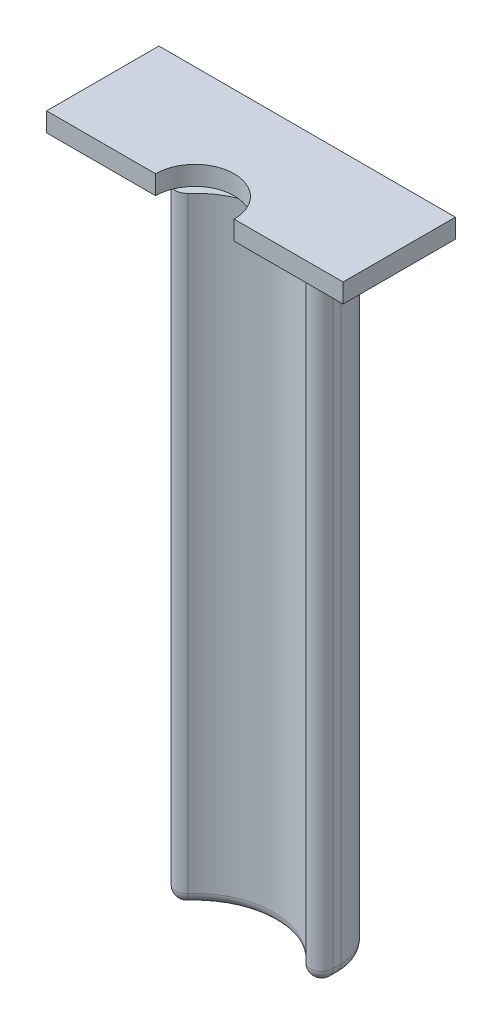
SolidWorks part; units mm, degrees
ref_plane "Plan de face" through (0, 0, 0) normal (0, 0, 1) x (1, 0, 0)
ref_plane "Plan de dessus" through (0, 0, 0) normal (0, 1, 0) x (1, 0, 0)
ref_plane "Plan de droite" through (0, 0, 0) normal (1, 0, 0) x (0, 0, -1)
sketch "Esquisse1" plane through (0, 0, 0) normal (0, 0, 1) x (1, 0, 0)
  line L1 (0, 0) -> (26.4, 0)
  line L2 (0, 0) -> (0, 1.7)
  line L3 (0, 1.7) -> (26.4, 1.7)
  line L4 (26.4, 0) -> (26.4, 1.7)
  dimension "D1" = 1.7
  dimension "D2" = 26.4
extrude "Boss.-Extru.1" add sketch "Esquisse1" along normal blind 10
sketch "Esquisse2" plane through (0, 0, 0) normal (0, -1, 0) x (1, 0, 0)
  line L0 (0, 0) -> (26.4, 0) construction
  line L1 (6.2, 1) -> (20.2, 1)
  line L2 (6.2, 1) -> (6.2, 0)
  line L3 (6.2, 0) -> (20.2, 0)
  line L4 (20.2, 1) -> (20.2, 0)
  line L5 (13.2, 1) -> (13.2, 10) construction
  line L6 (0, 10) -> (26.4, 10) construction
  dimension "D1" = 1
  dimension "D2" = 14
extrude "Boss.-Extru.2" add sketch "Esquisse2" along normal blind 3
sketch "Esquisse3" plane through (0, -3, 0) normal (0, -1, 0) x (1, 0, 0)
  line L0 (6.2, 10) -> (6.2, 0)
  line L1 (6.2, 0) -> (20.2, 0)
  line L2 (20.2, 0) -> (20.2, 10)
  arc A0 (6.2, 10) -> (20.2, 10) centre (13.2, 10) ccw
  dimension "D1" = 7
  dimension "D2" = 10
extrude "Boss.-Extru.3" add sketch "Esquisse3" along normal blind 55
fillet "Congé1" radius 1 2 edges at (20.2, -30.5, 10) (6.2, -30.5, 10)
fillet "Congé2" radius 4 2 edges at (20.2, -29, 0) (6.2, -29, 0)
fillet "Congé3" radius 4 2 edges at (17.6142, 0, 0.2583) (8.7858, 0, 0.2583)
fillet "Congé4" radius 1 8 edges at (7.3716, -58, 1.1716) (6.2, -58, 4.3542) (6.8464, -58, 5.6439) (13.2, -58, 3) (19.5536, -58, 5.6439) (20.2, -58, 4.3542) (19.0284, -58, 1.1716) (13.2, -58, 0)
sketch "Esquisse4" plane through (0, 1.7, 0) normal (0, 1, 0) x (1, 0, 0)
  line L0 (26.4, 0) -> (0, 0) construction
  line L1 (13.2, -10) -> (13.2, 0) construction
  circle A0 centre (13.2, -10) radius 3.5
  dimension "D2" = 7
  dimension "D1" = 10
extrude "Enlèv. mat.-Extru.1" cut sketch "Esquisse4" against normal through all
